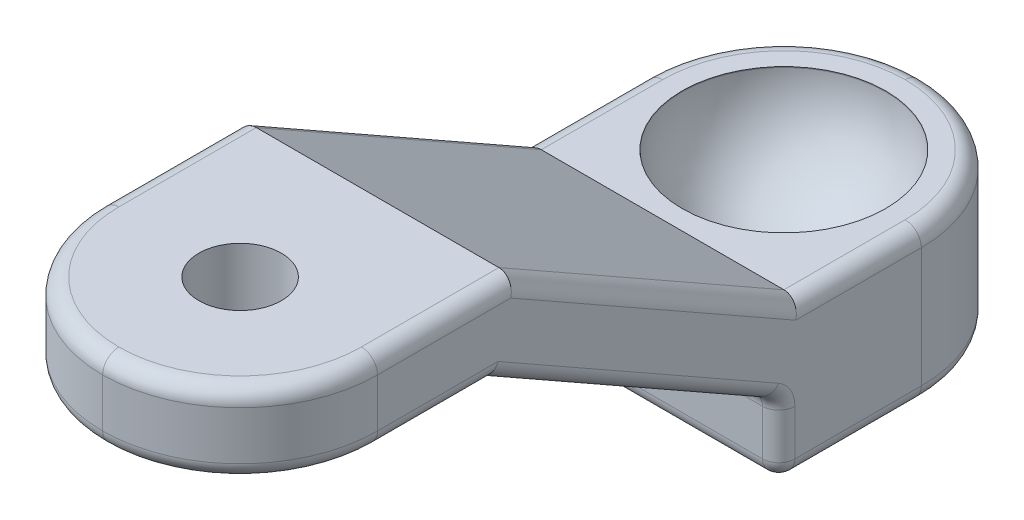
SolidWorks part; units mm, degrees
ref_plane "Front Plane" through (0, 0, 0) normal (0, 0, 1) x (1, 0, 0)
ref_plane "Top Plane" through (0, 0, 0) normal (0, 1, 0) x (1, 0, 0)
ref_plane "Right Plane" through (0, 0, 0) normal (1, 0, 0) x (0, 0, -1)
sketch "ProfileSketch1" plane through (0, 0, 0) normal (1, 0, 0) x (0, 0, -1)
  line L0 (0, 0) -> (34, 0)
  line L1 (34, 0) -> (69.2531, -20)
  line L2 (69.2531, -20) -> (101.2531, -20)
  line L3 (17, 0) -> (17, 2.8642) construction
  line L4 (85.2531, -20) -> (85.2531, 2.8642) construction
  dimension "D1" = 34
  dimension "D2" = 20
  dimension "D4" = 32
  dimension "D3" = 68.2531
extrude "ProfileExtrude-Thin1" add sketch "ProfileSketch1" along normal blind 34 thin thin type one direction wall 10
sketch "DomePadExtensionSketch1" plane through (0, -30, 0) normal (0, -1, 0) x (1, 0, 0)
  line L1 (0, -66.614) -> (34, -66.614)
  line L2 (0, -66.614) -> (0, -101.2531)
  line L3 (0, -101.2531) -> (34, -101.2531)
  line L4 (34, -66.614) -> (34, -101.2531)
extrude "DomePadExtensionBoss-Extrude1" add sketch "DomePadExtensionSketch1" along normal blind 8.8
fillet "Fillet1" radius 17 1 edges at (34, -5, 0)
fillet "Fillet2" radius 17 1 edges at (0, -5, 0)
sketch "FlangeNutHoleSketch4" plane through (0, 0, 0) normal (0, 1, 0) x (1, 0, 0)
  line L0 (0, 17) -> (0, 34) construction
  line L1 (34, 34) -> (0, 34) construction
  circle A0 centre (17, 17) radius 5.1
  dimension "D1" = 17
  dimension "D3" = 10.2
  dimension "D2" = 17
extrude "FlangeNutHoleCut-Extrude5" cut sketch "FlangeNutHoleSketch4" against normal through all
sketch "DomeIndentSketch6" plane through (0, -20, 0) normal (0, 1, 0) x (1, 0, 0)
  line L4 (0, 69.2531) -> (0, 101.2531) construction
  line L5 (34, 101.2531) -> (0, 101.2531) construction
  circle A0 centre (17, 84.2531) radius 12.6
  dimension "D2" = 17
  dimension "D1" = 25.2
  dimension "D3" = 17
extrude "DomeIndentCut-Extrude8" cut sketch "DomeIndentSketch6" against normal blind 0.1
dome "Dome2" faces to dome 1 distance 12.5 reverse direction yes elliptical dome no face at (17, -20.1, -71.6531) parameters "D1"=12.5
fillet "Fillet3" radius 17 1 edges at (34, -29.4, -101.2531)
fillet "Fillet4" radius 17 1 edges at (0, -29.4, -101.2531)
sketch "FlangeNutHolesSketch2" plane through (0, -10, 0) normal (0, -1, 0) x (1, 0, 0)
  line L0 (32, -31.2943) -> (32, -17) construction
  line L1 (34, -31.3609) -> (0, -31.3609) construction
  circle A0 centre (11.3431, -11.3431) radius 2
  circle A1 centre (22.6569, -11.3431) radius 2
  circle A2 centre (22.6569, -22.6569) radius 2
  circle A3 centre (11.3431, -22.6569) radius 2
  point P16 (17, -17)
  dimension "D2" = 4
  dimension "D1" = 8
  dimension "D4" = 8
  dimension "D3" = 4
fillet "BottomBoundaryFillet5" radius 2 14 edges at (0, -20, -48.9875) (34, -20, -48.9875) (34, -10, -24.1805) (29.0208, -10, -4.9792) (4.9792, -10, -4.9792) (0, -10, -24.1805) (34, -38.8, -75.4336) (29.0208, -38.8, -96.2739) (4.9792, -38.8, -96.2739) (34, -34.4, -66.614) (17, -38.8, -66.614) (0, -34.4, -66.614) (17, -30, -66.614) (0, -38.8, -75.4336)
extrude "FlangeNutHolesCut-Extrude1" cut sketch "FlangeNutHolesSketch2" against normal blind 4
fillet "Fillet6" radius 2 10 edges at (34, -10, -51.6266) (34, 0, -25.5) (29.0208, 0, -4.9792) (4.9792, 0, -4.9792) (0, 0, -25.5) (0, -10, -51.6266) (0, -20, -76.7531) (4.9792, -20, -96.2739) (34, -20, -76.7531) (29.0208, -20, -96.2739)
equation "\"D1@ProfileSketch1\"=\"BedSupportLeadScrewPadSize\""
equation "\"StandardWallThickness\"= 3mm"
equation "\"BedToBuildPlateStandoffPadSize\"= 10mm"
equation "\"BuildPlateStandoffHolesDistanceFromLeftOrRight\"= 7mm"
equation "\"BuildPlateStandoffHolesDistanceFromFrontOrBack\"= 41mm"
equation "\"DistanceFromBuildPlateSideToStepperHole\"= ( \"DistanceBetweenLeftToRightStepperHoles\" - \"BuildPlateWidth\" ) / 2'Equals 55.825"
equation "\"DistanceBetweenLeftToRightStepperHoles\"= \"FrontBackRailLength\" - \"StepperMountingHoleOffsetFromLeftOrRightSide\" * 2 - \"StepperMountingHoleDistance\"'Equals 461.65"
equation "\"FrontBackRailLength\"= 510mm"
equation "\"StepperMountingHoleOffsetFromLeftOrRightSide\"= \"StepperMountingHoleOffsetFromItsSide\" + \"RailThickness\""
equation "\"StepperMountingHoleDistance\"= 31mm'Spec"
equation "\"StepperMountingHoleOffsetFromItsSide\"= 5.5mm'Spec"
equation "\"RailThickness\"= .125in'Spec"
equation "\"LeadScrewNutPadSize\"= \"LeadScrewNutMountingHoleFlangeDiameter\" + 2mm'Equals 24"
equation "\"LeadScrewNutInnerShaftFlangeDiameter\"= 10.2mm'Spec"
equation "\"LeadScrewNutMountHoleDiameter\"= \"M3HeatInsertHoleDiameter\""
equation "\"LeadScrewNutMountingHoleFlangeDiameter\"= 22mm'Spec"
equation "\"LeadScrewNutMountingHoleDistance\"= 16mm'Spec"
equation "\"M3HeatInsertHoleDiameter\"= 4mm'Spec"
equation "\"D1@Fillet1\"=\"BedSupportLeadScrewPadSize\"/2"
equation "\"D1@Fillet2\"=\"BedSupportLeadScrewPadSize\"/2"
equation "\"D1@FlangeNutHoleSketch4\"=\"BedSupportLeadScrewPadSize\"  / 2"
equation "\"D2@FlangeNutHoleSketch4\"=\"BedSupportLeadScrewPadSize\" / 2"
equation "\"D3@FlangeNutHoleSketch4\" = \"LeadScrewNutInnerShaftFlangeDiameter\""
equation "\"D2@DomeIndentSketch6\" = \"BedSupportLeadScrewPadSize\" / 2"
equation "\"D3@DomeIndentSketch6\" = \"BedSupportLeadScrewPadSize\" / 2"
equation "\"BedSpringHoleSize\"= 3mm"
equation "\"BuildPlateWidth\"= 350mm'Spec"
equation "\"BuildPlateLength\"= 350mm'Spec"
equation "\"BuildPlateBoreDiameter\"= 5mm'Spec"
equation "\"BuildPlateBoreDepth\"= 3mm'Spec"
equation "\"BuildPlateDepth\"= 8mm'Spec"
equation "\"BuildPlateFlankingHoles\"= 38mm"
equation "\"BuildPlateStandoffHolesDistanceFromFront\"= 7mm"
equation "\"BedSupportLeadScrewPadSize\"= \"LeadScrewNutPadSize\" + 10mm"
equation "\"D1@ProfileExtrude-Thin1\"=\"BedSupportLeadScrewPadSize\""
equation "\"BuildPlateBallDiameter\"= 12mm"
equation "\"BedSupportBuildPlatePadSize\"= \"BuildPlateBallDiameter\" + 20mm"
equation "\"D4@ProfileSketch1\"=\"BedSupportBuildPlatePadSize\""
equation "\"D3@ProfileSketch1\"= \"HypotonusOfStepperAndBuildPlateHoles\" + 1mm'Odd, both physical and CAD required 1mm extra"
equation "\"D1@Fillet3\"=\"BedSupportLeadScrewPadSize\"/2"
equation "\"D1@Fillet4\"=\"BedSupportLeadScrewPadSize\"/2"
equation "\"HypotonusOfStepperAndBuildPlateHoles\"= sqr ( ( \"DistanceFromBuildPlateSideToStepperHole\" + \"BuildPlateStandoffHolesDistanceFromLeftOrRight\" ) ^ 2 + ( \"BuildPlateStandoffHolesDistanceFromFrontOrBack\" - \"BedSupportLeadScrewPadSize\" / 2 ) ^ 2 )"
equation "\"D1@FlangeNutHolesCut-Extrude1\" = \"M3HeatInsertHoleDiameter\""
equation "\"D1@FlangeNutHolesSketch2\"=\"LeadScrewNutMountingHoleDistance\"/2"
equation "\"D2@FlangeNutHolesSketch2\"=\"M3HeatInsertHoleDiameter\""
equation "\"D4@FlangeNutHolesSketch2\"=\"LeadScrewNutMountingHoleDistance\"/2"
equation "\"BallNutDiameter\"= \"BallJointDiameter\" + .2mm'Added .2mm for filament expansion"
equation "\"D1@DomeIndentSketch6\"=\"BallNutDiameter\""
equation "\"D1@DomePadExtensionBoss-Extrude1\" = \"BedSupportBuildPlatePadSize\" - \"BallNutDiameter\" + 2mm"
equation "\"BallJointDiameter\"= 25mm"
